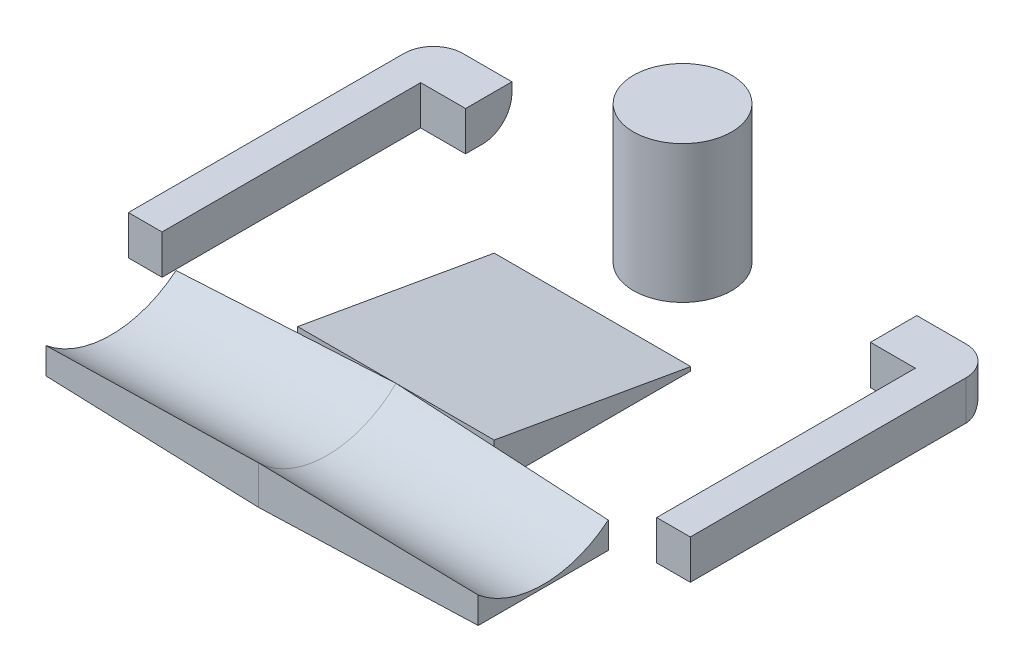
SolidWorks part; units mm, degrees
ref_plane "Front Plane" through (0, 0, 0) normal (0, 0, 1) x (1, 0, 0)
ref_plane "Top Plane" through (0, 0, 0) normal (0, 1, 0) x (1, 0, 0)
ref_plane "Right Plane" through (0, 0, 0) normal (1, 0, 0) x (0, 0, -1)
sketch "Sketch2" plane through (0, 0, 0) normal (0, 1, 0) x (1, 0, 0)
  line L0 (-95.95, 172.031) -> (-97.0155, 172.1902)
  line L1 (-97.0155, 172.1902) -> (-97.8001, 172.331)
  line L2 (95.95, 172.031) -> (97.0155, 172.1902)
  line L3 (97.0155, 172.1902) -> (97.8001, 172.331)
  line L4 (-106.3449, 171.5223) -> (-95.95, 171.5223)
  line L5 (-53.65, 171.5223) -> (-37.3449, 171.5223)
  line L6 (-37.3449, 189.5223) -> (-53.65, 189.5223)
  line L7 (-95.95, 189.5223) -> (-106.3449, 189.5223)
  line L8 (-106.3449, 179.9616) -> (-111.928, 179.9616)
  line L9 (-113.1433, 179.9616) -> (-121.3449, 179.9616)
  line L10 (-121.3449, 172.4616) -> (-106.3449, 172.4616)
  line L11 (-106.3449, 189.5223) -> (-106.3449, 176.1788)
  line L12 (-106.3449, 175.2767) -> (-106.3449, 171.5223)
  line L13 (-37.3449, 189.5223) -> (-37.3449, 181.131)
  line L14 (-37.3449, 180.0634) -> (-37.3449, 171.5223)
  line L15 (-121.3449, 172.4616) -> (-121.3449, 179.9616)
  line L16 (92.95, 159.181) -> (56.65, 159.181)
  line L17 (53.65, 162.181) -> (56.65, 159.181)
  line L18 (95.95, 198.481) -> (92.95, 201.481)
  line L19 (95.95, 172.331) -> (101.95, 172.331)
  line L20 (53.65, 198.481) -> (56.65, 201.481)
  line L21 (95.95, 198.481) -> (95.95, 188.331)
  line L22 (95.95, 172.331) -> (95.95, 162.181)
  line L23 (56.65, 201.481) -> (92.95, 201.481)
  line L24 (53.65, 162.181) -> (53.65, 198.481)
  line L25 (95.95, 162.181) -> (92.95, 159.181)
  line L26 (101.95, 188.331) -> (101.95, 172.331)
  line L27 (95.95, 188.331) -> (101.95, 188.331)
  line L28 (-53.65, 162.181) -> (-56.65, 159.181)
  line L29 (-56.65, 159.181) -> (-92.95, 159.181)
  line L30 (-95.95, 162.181) -> (-92.95, 159.181)
  line L31 (-95.95, 162.181) -> (-95.95, 172.331)
  line L32 (-95.95, 172.331) -> (-101.95, 172.331)
  line L33 (-101.95, 172.331) -> (-101.95, 188.331)
  line L34 (-95.95, 188.331) -> (-101.95, 188.331)
  line L35 (-95.95, 188.331) -> (-95.95, 198.481)
  line L36 (-53.65, 198.481) -> (-53.65, 162.181)
  line L37 (-92.95, 201.481) -> (-56.65, 201.481)
  line L38 (-95.95, 198.481) -> (-92.95, 201.481)
  line L39 (-53.65, 198.481) -> (-56.65, 201.481)
  line L40 (87.55, 164.831) -> (87.715, 164.831)
  line L41 (-56.55, 195.831) -> (-56.715, 195.831)
  line L42 (-87.55, 164.831) -> (-87.715, 164.831)
  line L43 (56.55, 164.831) -> (56.715, 164.831)
  line L44 (-87.55, 195.831) -> (-87.715, 195.831)
  line L45 (87.55, 195.831) -> (87.715, 195.831)
  line L46 (56.55, 195.831) -> (56.715, 195.831)
  line L47 (-56.55, 164.831) -> (-56.715, 164.831)
  line L48 (-15, 180.331) -> (-7, 180.331)
  line L49 (-32.5736, 137.9046) -> (-26.9167, 132.2478)
  line L50 (-75, 120.331) -> (-75, 112.331)
  line L51 (-117.4264, 137.9046) -> (-123.0833, 132.2478)
  line L52 (-135, 180.331) -> (-143, 180.331)
  line L53 (-117.4264, 222.7574) -> (-123.0833, 228.4143)
  line L54 (-75, 240.331) -> (-75, 248.331)
  line L55 (-32.5736, 222.7574) -> (-26.9167, 228.4143)
  line L56 (32.5736, 222.7574) -> (26.9167, 228.4143)
  line L57 (75, 240.331) -> (75, 248.331)
  line L58 (117.4264, 222.7574) -> (123.0833, 228.4143)
  line L59 (135, 180.331) -> (143, 180.331)
  line L60 (117.4264, 137.9046) -> (123.0833, 132.2478)
  line L61 (75, 120.331) -> (75, 112.331)
  line L62 (32.5736, 137.9046) -> (26.9167, 132.2478)
  line L63 (15, 180.331) -> (7, 180.331)
  circle A0 centre (90.3, 164.831) radius 2.585
  circle A1 centre (90.3, 164.831) radius 2.75
  circle A2 centre (-59.3, 195.831) radius 2.585
  circle A3 centre (-59.3, 195.831) radius 2.75
  circle A4 centre (-90.3, 164.831) radius 2.585
  circle A5 centre (-90.3, 164.831) radius 2.75
  circle A6 centre (59.3, 164.831) radius 2.585
  circle A7 centre (59.3, 164.831) radius 2.75
  circle A8 centre (-90.3, 195.831) radius 2.585
  circle A9 centre (-90.3, 195.831) radius 2.75
  circle A10 centre (90.3, 195.831) radius 2.585
  circle A11 centre (90.3, 195.831) radius 2.75
  circle A12 centre (59.3, 195.831) radius 2.585
  circle A13 centre (59.3, 195.831) radius 2.75
  circle A14 centre (-59.3, 164.831) radius 2.585
  circle A15 centre (-59.3, 164.831) radius 2.75
  arc A16 (59.3, 161.956) -> (59.3, 167.706) centre (59.3, 164.831) ccw
  arc A17 (59.3, 167.706) -> (59.3, 161.956) centre (59.3, 164.831) ccw
  arc A18 (90.3, 192.956) -> (90.3, 198.706) centre (90.3, 195.831) ccw
  arc A19 (90.3, 198.706) -> (90.3, 192.956) centre (90.3, 195.831) ccw
  arc A20 (59.3, 192.956) -> (59.3, 198.706) centre (59.3, 195.831) ccw
  arc A21 (59.3, 198.706) -> (59.3, 192.956) centre (59.3, 195.831) ccw
  arc A22 (90.3, 161.956) -> (90.3, 167.706) centre (90.3, 164.831) ccw
  arc A23 (90.3, 167.706) -> (90.3, 161.956) centre (90.3, 164.831) ccw
  arc A24 (-59.3, 198.706) -> (-59.3, 192.956) centre (-59.3, 195.831) ccw
  arc A25 (-59.3, 192.956) -> (-59.3, 198.706) centre (-59.3, 195.831) ccw
  arc A26 (-90.3, 198.706) -> (-90.3, 192.956) centre (-90.3, 195.831) ccw
  arc A27 (-90.3, 192.956) -> (-90.3, 198.706) centre (-90.3, 195.831) ccw
  arc A28 (-90.3, 167.706) -> (-90.3, 161.956) centre (-90.3, 164.831) ccw
  arc A29 (-90.3, 161.956) -> (-90.3, 167.706) centre (-90.3, 164.831) ccw
  arc A30 (-59.3, 167.706) -> (-59.3, 161.956) centre (-59.3, 164.831) ccw
  arc A31 (-59.3, 161.956) -> (-59.3, 167.706) centre (-59.3, 164.831) ccw
  arc A32 (91.55, 165.5527) -> (91.55, 164.1093) centre (90.3, 164.831) ccw
  arc A33 (91.55, 164.1093) -> (91.55, 165.5527) centre (90.3, 164.831) ccw
  arc A34 (-60.55, 196.5527) -> (-59.3, 197.2744) centre (-59.3, 195.831) ccw
  arc A35 (-59.3, 197.2744) -> (-60.55, 196.5527) centre (-59.3, 195.831) ccw
  arc A36 (-91.55, 165.5527) -> (-90.3, 166.2744) centre (-90.3, 164.831) ccw
  arc A37 (-90.3, 166.2744) -> (-91.55, 165.5527) centre (-90.3, 164.831) ccw
  arc A38 (60.55, 164.1093) -> (59.3, 163.3877) centre (59.3, 164.831) ccw
  arc A39 (59.3, 163.3877) -> (60.55, 164.1093) centre (59.3, 164.831) ccw
  arc A40 (-91.55, 196.5527) -> (-90.3, 197.2744) centre (-90.3, 195.831) ccw
  arc A41 (-90.3, 197.2744) -> (-91.55, 196.5527) centre (-90.3, 195.831) ccw
  arc A42 (91.55, 195.1093) -> (90.3, 194.3877) centre (90.3, 195.831) ccw
  arc A43 (90.3, 194.3877) -> (91.55, 195.1093) centre (90.3, 195.831) ccw
  arc A44 (60.55, 195.1093) -> (59.3, 194.3877) centre (59.3, 195.831) ccw
  arc A45 (59.3, 194.3877) -> (60.55, 195.1093) centre (59.3, 195.831) ccw
  arc A46 (-58.05, 165.5527) -> (-58.05, 164.1093) centre (-59.3, 164.831) ccw
  arc A47 (-58.05, 164.1093) -> (-58.05, 165.5527) centre (-59.3, 164.831) ccw
  arc A48 (-16.2563, 192.5448) -> (-7, 180.331) centre (1.2261, 196.1796) ccw
  arc A49 (-24.8255, 147.4294) -> (-26.9167, 132.2478) centre (-9.8933, 137.6376) ccw
  arc A50 (-62.7863, 121.5873) -> (-75, 112.331) centre (-59.1514, 104.1049) ccw
  arc A51 (-107.9017, 130.1565) -> (-123.0833, 132.2478) centre (-117.6934, 115.2243) ccw
  arc A52 (-133.7437, 168.1173) -> (-143, 180.331) centre (-151.2261, 164.4824) ccw
  arc A53 (-125.1745, 213.2327) -> (-123.0833, 228.4143) centre (-140.1067, 223.0244) ccw
  arc A54 (-87.2137, 239.0747) -> (-75, 248.331) centre (-90.8486, 256.5572) ccw
  arc A55 (-42.0983, 230.5055) -> (-26.9167, 228.4143) centre (-32.3066, 245.4377) ccw
  arc A56 (-42.0983, 230.5055) -> (-75, 240.331) centre (-75, 180.331) ccw
  arc A57 (-16.5125, 186.3853) -> (-35.0706, 223.4945) centre (-75, 180.331) ccw
  arc A58 (-37.9241, 225.9689) -> (-77.2868, 239.0865) centre (-75, 180.331) ccw
  arc A59 (-81.0542, 238.8185) -> (-118.1635, 220.2604) centre (-75, 180.331) ccw
  arc A60 (-120.6379, 217.4069) -> (-133.7555, 178.0442) centre (-75, 180.331) ccw
  arc A61 (-133.4875, 174.2768) -> (-114.9294, 137.1676) centre (-75, 180.331) ccw
  arc A62 (-112.0759, 134.6931) -> (-72.7132, 121.5755) centre (-75, 180.331) ccw
  arc A63 (-68.9458, 121.8435) -> (-31.8365, 140.4017) centre (-75, 180.331) ccw
  arc A64 (-29.3621, 143.2551) -> (-16.2445, 182.6179) centre (-75, 180.331) ccw
  arc A65 (-29.3621, 143.2551) -> (-53.65, 188.5756) centre (-58.2384, 156.9482) ccw
  arc A66 (-31.8365, 140.4017) -> (-53.65, 187.767) centre (-58.2384, 156.9482) ccw
  arc A67 (-68.9458, 121.8435) -> (-53.65, 170.4834) centre (-79.6819, 151.9447) ccw
  arc A68 (-72.7132, 121.5755) -> (-53.65, 169.0675) centre (-79.6819, 151.9447) ccw
  arc A69 (-112.0759, 134.6931) -> (-66.7271, 159.181) centre (-98.3828, 163.5694) ccw
  arc A70 (-114.9294, 137.1676) -> (-67.5349, 159.181) centre (-98.3828, 163.5694) ccw
  arc A71 (-133.4875, 174.2768) -> (-84.57, 159.181) centre (-103.3864, 185.0129) ccw
  arc A72 (-133.7555, 178.0442) -> (-85.9633, 159.181) centre (-103.3864, 185.0129) ccw
  arc A73 (-120.6379, 217.4069) -> (-101.95, 173.4229) centre (-91.7616, 203.7138) ccw
  arc A74 (-118.1635, 220.2604) -> (-101.95, 174.2682) centre (-91.7616, 203.7138) ccw
  arc A75 (-81.0542, 238.8185) -> (-95.95, 189.6295) centre (-70.3181, 208.7174) ccw
  arc A76 (-77.2868, 239.0865) -> (-95.95, 191.0014) centre (-70.3181, 208.7174) ccw
  arc A77 (-37.9241, 225.9689) -> (-83.2729, 201.481) centre (-51.6172, 197.0926) ccw
  arc A78 (-35.0706, 223.4945) -> (-82.4651, 201.481) centre (-51.6172, 197.0926) ccw
  arc A79 (-16.5125, 186.3853) -> (-65.43, 201.481) centre (-46.6136, 175.6491) ccw
  arc A80 (-16.2445, 182.6179) -> (-64.0367, 201.481) centre (-46.6136, 175.6491) ccw
  arc A81 (-16.2563, 192.5448) -> (-32.5736, 222.7574) centre (-75, 180.331) ccw
  arc A82 (-24.8255, 147.4294) -> (-15, 180.331) centre (-75, 180.331) ccw
  arc A83 (-107.9017, 130.1565) -> (-75, 120.331) centre (-75, 180.331) ccw
  arc A84 (-133.7437, 168.1173) -> (-117.4264, 137.9046) centre (-75, 180.331) ccw
  arc A85 (-125.1745, 213.2327) -> (-135, 180.331) centre (-75, 180.331) ccw
  arc A86 (-87.2137, 239.0747) -> (-117.4264, 222.7574) centre (-75, 180.331) ccw
  arc A87 (-62.7863, 121.5873) -> (-32.5736, 137.9046) centre (-75, 180.331) ccw
  arc A88 (26.9167, 228.4143) -> (42.0983, 230.5055) centre (32.3066, 245.4377) ccw
  arc A89 (75, 240.331) -> (42.0983, 230.5055) centre (75, 180.331) ccw
  arc A90 (75, 248.331) -> (87.2137, 239.0747) centre (90.8486, 256.5572) ccw
  arc A91 (117.4264, 222.7574) -> (87.2137, 239.0747) centre (75, 180.331) ccw
  arc A92 (123.0833, 228.4143) -> (125.1745, 213.2327) centre (140.1067, 223.0244) ccw
  arc A93 (135, 180.331) -> (125.1745, 213.2327) centre (75, 180.331) ccw
  arc A94 (143, 180.331) -> (133.7437, 168.1173) centre (151.2261, 164.4824) ccw
  arc A95 (117.4264, 137.9046) -> (133.7437, 168.1173) centre (75, 180.331) ccw
  arc A96 (123.0833, 132.2478) -> (107.9017, 130.1565) centre (117.6934, 115.2243) ccw
  arc A97 (75, 120.331) -> (107.9017, 130.1565) centre (75, 180.331) ccw
  arc A98 (75, 112.331) -> (62.7863, 121.5873) centre (59.1514, 104.1049) ccw
  arc A99 (32.5736, 137.9046) -> (62.7863, 121.5873) centre (75, 180.331) ccw
  arc A100 (26.9167, 132.2478) -> (24.8255, 147.4294) centre (9.8933, 137.6376) ccw
  arc A101 (15, 180.331) -> (24.8255, 147.4294) centre (75, 180.331) ccw
  arc A102 (7, 180.331) -> (16.2563, 192.5448) centre (-1.2261, 196.1796) ccw
  arc A103 (32.5736, 222.7574) -> (16.2563, 192.5448) centre (75, 180.331) ccw
  arc A104 (53.65, 170.4834) -> (68.9458, 121.8435) centre (79.6819, 151.9447) ccw
  arc A105 (53.65, 187.767) -> (31.8365, 140.4017) centre (58.2384, 156.9482) ccw
  arc A106 (53.65, 169.0675) -> (72.7132, 121.5755) centre (79.6819, 151.9447) ccw
  arc A107 (67.5349, 159.181) -> (114.9294, 137.1676) centre (98.3828, 163.5694) ccw
  arc A108 (85.9633, 159.181) -> (133.7555, 178.0442) centre (103.3864, 185.0129) ccw
  arc A109 (133.7555, 178.0442) -> (120.6379, 217.4069) centre (75, 180.331) ccw
  arc A110 (101.95, 174.2682) -> (118.1635, 220.2604) centre (91.7616, 203.7138) ccw
  arc A111 (95.95, 191.0014) -> (77.2868, 239.0865) centre (70.3181, 208.7174) ccw
  arc A112 (77.2868, 239.0865) -> (37.9241, 225.9689) centre (75, 180.331) ccw
  arc A113 (82.4651, 201.481) -> (35.0706, 223.4945) centre (51.6172, 197.0926) ccw
  arc A114 (64.0367, 201.481) -> (16.2445, 182.6179) centre (46.6136, 175.6491) ccw
  arc A115 (65.43, 201.481) -> (16.5125, 186.3853) centre (46.6136, 175.6491) ccw
  arc A116 (101.95, 173.4229) -> (120.6379, 217.4069) centre (91.7616, 203.7138) ccw
  arc A117 (35.0706, 223.4945) -> (16.5125, 186.3853) centre (75, 180.331) ccw
  arc A118 (95.95, 189.6295) -> (81.0542, 238.8185) centre (70.3181, 208.7174) ccw
  arc A119 (83.2729, 201.481) -> (37.9241, 225.9689) centre (51.6172, 197.0926) ccw
  arc A120 (118.1635, 220.2604) -> (81.0542, 238.8185) centre (75, 180.331) ccw
  arc A121 (114.9294, 137.1676) -> (133.4875, 174.2768) centre (75, 180.331) ccw
  arc A122 (72.7132, 121.5755) -> (112.0759, 134.6931) centre (75, 180.331) ccw
  arc A123 (31.8365, 140.4017) -> (68.9458, 121.8435) centre (75, 180.331) ccw
  arc A124 (16.2445, 182.6179) -> (29.3621, 143.2551) centre (75, 180.331) ccw
  arc A125 (53.65, 188.5756) -> (29.3621, 143.2551) centre (58.2384, 156.9482) ccw
  arc A126 (66.7271, 159.181) -> (112.0759, 134.6931) centre (98.3828, 163.5694) ccw
  arc A127 (84.57, 159.181) -> (133.4875, 174.2768) centre (103.3864, 185.0129) ccw
  spline S0 degree 3 poles (90.3, 163.3877) (90.4198, 163.4568) (90.6406, 163.5843) (90.9748, 163.7772) (91.2766, 163.9515) (91.454, 164.0539) (91.55, 164.1093) knots 0 0 0 0 0.300011 0.553083 0.757954 1 1 1 1
  spline S1 degree 3 poles (89.05, 164.1093) (89.1698, 164.0402) (89.3906, 163.9127) (89.7248, 163.7197) (90.0266, 163.5455) (90.204, 163.4431) (90.3, 163.3877) knots 0 0 0 0 0.300011 0.553083 0.757954 1 1 1 1
  spline S2 degree 3 poles (89.05, 165.5527) (89.05, 165.4144) (89.05, 165.1594) (89.05, 164.7735) (89.05, 164.425) (89.05, 164.2202) (89.05, 164.1093) knots 0 0 0 0 0.300011 0.553083 0.757954 1 1 1 1
  spline S3 degree 3 poles (90.3, 166.2744) (90.1802, 166.2052) (89.9594, 166.0777) (89.6252, 165.8848) (89.3234, 165.7106) (89.146, 165.6082) (89.05, 165.5527) knots 0 0 0 0 0.300011 0.553083 0.757954 1 1 1 1
  spline S4 degree 3 poles (91.55, 165.5527) (91.4302, 165.6219) (91.2094, 165.7494) (90.8752, 165.9423) (90.5734, 166.1166) (90.396, 166.2189) (90.3, 166.2744) knots 0 0 0 0 0.300011 0.553083 0.757954 1 1 1 1
  spline S5 degree 3 poles (91.55, 164.1093) (91.55, 164.2477) (91.55, 164.5027) (91.55, 164.8885) (91.55, 165.237) (91.55, 165.4418) (91.55, 165.5527) knots 0 0 0 0 0.300011 0.553083 0.757954 1 1 1 1
  spline S6 degree 3 poles (-58.05, 196.5527) (-58.1698, 196.6219) (-58.3906, 196.7494) (-58.7248, 196.9423) (-59.0266, 197.1166) (-59.204, 197.2189) (-59.3, 197.2744) knots 0 0 0 0 0.300011 0.553083 0.757954 1 1 1 1
  spline S7 degree 3 poles (-58.05, 195.1093) (-58.05, 195.2477) (-58.05, 195.5027) (-58.05, 195.8885) (-58.05, 196.237) (-58.05, 196.4418) (-58.05, 196.5527) knots 0 0 0 0 0.300011 0.553083 0.757954 1 1 1 1
  spline S8 degree 3 poles (-59.3, 194.3877) (-59.1802, 194.4568) (-58.9594, 194.5843) (-58.6252, 194.7772) (-58.3234, 194.9515) (-58.146, 195.0539) (-58.05, 195.1093) knots 0 0 0 0 0.300011 0.553083 0.757954 1 1 1 1
  spline S9 degree 3 poles (-60.55, 195.1093) (-60.4302, 195.0402) (-60.2094, 194.9127) (-59.8752, 194.7197) (-59.5734, 194.5455) (-59.396, 194.4431) (-59.3, 194.3877) knots 0 0 0 0 0.300011 0.553083 0.757954 1 1 1 1
  spline S10 degree 3 poles (-60.55, 196.5527) (-60.55, 196.4144) (-60.55, 196.1594) (-60.55, 195.7735) (-60.55, 195.425) (-60.55, 195.2202) (-60.55, 195.1093) knots 0 0 0 0 0.300011 0.553083 0.757954 1 1 1 1
  spline S11 degree 3 poles (-59.3, 197.2744) (-59.4198, 197.2052) (-59.6406, 197.0777) (-59.9748, 196.8848) (-60.2766, 196.7106) (-60.454, 196.6082) (-60.55, 196.5527) knots 0 0 0 0 0.300011 0.553083 0.757954 1 1 1 1
  spline S12 degree 3 poles (-89.05, 165.5527) (-89.1698, 165.6219) (-89.3906, 165.7494) (-89.7248, 165.9423) (-90.0266, 166.1166) (-90.204, 166.2189) (-90.3, 166.2744) knots 0 0 0 0 0.300011 0.553083 0.757954 1 1 1 1
  spline S13 degree 3 poles (-89.05, 164.1093) (-89.05, 164.2477) (-89.05, 164.5027) (-89.05, 164.8885) (-89.05, 165.237) (-89.05, 165.4418) (-89.05, 165.5527) knots 0 0 0 0 0.300011 0.553083 0.757954 1 1 1 1
  spline S14 degree 3 poles (-90.3, 163.3877) (-90.1802, 163.4568) (-89.9594, 163.5843) (-89.6252, 163.7772) (-89.3234, 163.9515) (-89.146, 164.0539) (-89.05, 164.1093) knots 0 0 0 0 0.300011 0.553083 0.757954 1 1 1 1
  spline S15 degree 3 poles (-91.55, 165.5527) (-91.55, 165.4144) (-91.55, 165.1594) (-91.55, 164.7735) (-91.55, 164.425) (-91.55, 164.2202) (-91.55, 164.1093) knots 0 0 0 0 0.300011 0.553083 0.757954 1 1 1 1
  spline S16 degree 3 poles (-91.55, 164.1093) (-91.4302, 164.0402) (-91.2094, 163.9127) (-90.8752, 163.7197) (-90.5734, 163.5455) (-90.396, 163.4431) (-90.3, 163.3877) knots 0 0 0 0 0.300011 0.553083 0.757954 1 1 1 1
  spline S17 degree 3 poles (-90.3, 166.2744) (-90.4198, 166.2052) (-90.6406, 166.0777) (-90.9748, 165.8848) (-91.2766, 165.7106) (-91.454, 165.6082) (-91.55, 165.5527) knots 0 0 0 0 0.300011 0.553083 0.757954 1 1 1 1
  spline S18 degree 3 poles (58.05, 164.1093) (58.1698, 164.0402) (58.3906, 163.9127) (58.7248, 163.7197) (59.0266, 163.5455) (59.204, 163.4431) (59.3, 163.3877) knots 0 0 0 0 0.300011 0.553083 0.757954 1 1 1 1
  spline S19 degree 3 poles (58.05, 165.5527) (58.05, 165.4144) (58.05, 165.1594) (58.05, 164.7735) (58.05, 164.425) (58.05, 164.2202) (58.05, 164.1093) knots 0 0 0 0 0.300011 0.553083 0.757954 1 1 1 1
  spline S20 degree 3 poles (59.3, 166.2744) (59.1802, 166.2052) (58.9594, 166.0777) (58.6252, 165.8848) (58.3234, 165.7106) (58.146, 165.6082) (58.05, 165.5527) knots 0 0 0 0 0.300011 0.553083 0.757954 1 1 1 1
  spline S21 degree 3 poles (60.55, 165.5527) (60.4302, 165.6219) (60.2094, 165.7494) (59.8752, 165.9423) (59.5734, 166.1166) (59.396, 166.2189) (59.3, 166.2744) knots 0 0 0 0 0.300011 0.553083 0.757954 1 1 1 1
  spline S22 degree 3 poles (60.55, 164.1093) (60.55, 164.2477) (60.55, 164.5027) (60.55, 164.8885) (60.55, 165.237) (60.55, 165.4418) (60.55, 165.5527) knots 0 0 0 0 0.300011 0.553083 0.757954 1 1 1 1
  spline S23 degree 3 poles (59.3, 163.3877) (59.4198, 163.4568) (59.6406, 163.5843) (59.9748, 163.7772) (60.2766, 163.9515) (60.454, 164.0539) (60.55, 164.1093) knots 0 0 0 0 0.300011 0.553083 0.757954 1 1 1 1
  spline S24 degree 3 poles (-89.05, 196.5527) (-89.1698, 196.6219) (-89.3906, 196.7494) (-89.7248, 196.9423) (-90.0266, 197.1166) (-90.204, 197.2189) (-90.3, 197.2744) knots 0 0 0 0 0.300011 0.553083 0.757954 1 1 1 1
  spline S25 degree 3 poles (-91.55, 195.1093) (-91.4302, 195.0402) (-91.2094, 194.9127) (-90.8752, 194.7197) (-90.5734, 194.5455) (-90.396, 194.4431) (-90.3, 194.3877) knots 0 0 0 0 0.300011 0.553083 0.757954 1 1 1 1
  spline S26 degree 3 poles (-89.05, 195.1093) (-89.05, 195.2477) (-89.05, 195.5027) (-89.05, 195.8885) (-89.05, 196.237) (-89.05, 196.4418) (-89.05, 196.5527) knots 0 0 0 0 0.300011 0.553083 0.757954 1 1 1 1
  spline S27 degree 3 poles (-90.3, 194.3877) (-90.1802, 194.4568) (-89.9594, 194.5843) (-89.6252, 194.7772) (-89.3234, 194.9515) (-89.146, 195.0539) (-89.05, 195.1093) knots 0 0 0 0 0.300011 0.553083 0.757954 1 1 1 1
  spline S28 degree 3 poles (-91.55, 196.5527) (-91.55, 196.4144) (-91.55, 196.1594) (-91.55, 195.7735) (-91.55, 195.425) (-91.55, 195.2202) (-91.55, 195.1093) knots 0 0 0 0 0.300011 0.553083 0.757954 1 1 1 1
  spline S29 degree 3 poles (-90.3, 197.2744) (-90.4198, 197.2052) (-90.6406, 197.0777) (-90.9748, 196.8848) (-91.2766, 196.7106) (-91.454, 196.6082) (-91.55, 196.5527) knots 0 0 0 0 0.300011 0.553083 0.757954 1 1 1 1
  spline S30 degree 3 poles (89.05, 195.1093) (89.1698, 195.0402) (89.3906, 194.9127) (89.7248, 194.7197) (90.0266, 194.5455) (90.204, 194.4431) (90.3, 194.3877) knots 0 0 0 0 0.300011 0.553083 0.757954 1 1 1 1
  spline S31 degree 3 poles (91.55, 196.5527) (91.4302, 196.6219) (91.2094, 196.7494) (90.8752, 196.9423) (90.5734, 197.1166) (90.396, 197.2189) (90.3, 197.2744) knots 0 0 0 0 0.300011 0.553083 0.757954 1 1 1 1
  spline S32 degree 3 poles (91.55, 195.1093) (91.55, 195.2477) (91.55, 195.5027) (91.55, 195.8885) (91.55, 196.237) (91.55, 196.4418) (91.55, 196.5527) knots 0 0 0 0 0.300011 0.553083 0.757954 1 1 1 1
  spline S33 degree 3 poles (90.3, 197.2744) (90.1802, 197.2052) (89.9594, 197.0777) (89.6252, 196.8848) (89.3234, 196.7106) (89.146, 196.6082) (89.05, 196.5527) knots 0 0 0 0 0.300011 0.553083 0.757954 1 1 1 1
  spline S34 degree 3 poles (89.05, 196.5527) (89.05, 196.4144) (89.05, 196.1594) (89.05, 195.7735) (89.05, 195.425) (89.05, 195.2202) (89.05, 195.1093) knots 0 0 0 0 0.300011 0.553083 0.757954 1 1 1 1
  spline S35 degree 3 poles (90.3, 194.3877) (90.4198, 194.4568) (90.6406, 194.5843) (90.9748, 194.7772) (91.2766, 194.9515) (91.454, 195.0539) (91.55, 195.1093) knots 0 0 0 0 0.300011 0.553083 0.757954 1 1 1 1
  spline S36 degree 3 poles (58.05, 195.1093) (58.1698, 195.0402) (58.3906, 194.9127) (58.7248, 194.7197) (59.0266, 194.5455) (59.204, 194.4431) (59.3, 194.3877) knots 0 0 0 0 0.300011 0.553083 0.757954 1 1 1 1
  spline S37 degree 3 poles (58.05, 196.5527) (58.05, 196.4144) (58.05, 196.1594) (58.05, 195.7735) (58.05, 195.425) (58.05, 195.2202) (58.05, 195.1093) knots 0 0 0 0 0.300011 0.553083 0.757954 1 1 1 1
  spline S38 degree 3 poles (59.3, 197.2744) (59.1802, 197.2052) (58.9594, 197.0777) (58.6252, 196.8848) (58.3234, 196.7106) (58.146, 196.6082) (58.05, 196.5527) knots 0 0 0 0 0.300011 0.553083 0.757954 1 1 1 1
  spline S39 degree 3 poles (60.55, 196.5527) (60.4302, 196.6219) (60.2094, 196.7494) (59.8752, 196.9423) (59.5734, 197.1166) (59.396, 197.2189) (59.3, 197.2744) knots 0 0 0 0 0.300011 0.553083 0.757954 1 1 1 1
  spline S40 degree 3 poles (60.55, 195.1093) (60.55, 195.2477) (60.55, 195.5027) (60.55, 195.8885) (60.55, 196.237) (60.55, 196.4418) (60.55, 196.5527) knots 0 0 0 0 0.300011 0.553083 0.757954 1 1 1 1
  spline S41 degree 3 poles (59.3, 194.3877) (59.4198, 194.4568) (59.6406, 194.5843) (59.9748, 194.7772) (60.2766, 194.9515) (60.454, 195.0539) (60.55, 195.1093) knots 0 0 0 0 0.300011 0.553083 0.757954 1 1 1 1
  spline S42 degree 3 poles (-59.3, 163.3877) (-59.1802, 163.4568) (-58.9594, 163.5843) (-58.6252, 163.7772) (-58.3234, 163.9515) (-58.146, 164.0539) (-58.05, 164.1093) knots 0 0 0 0 0.300011 0.553083 0.757954 1 1 1 1
  spline S43 degree 3 poles (-60.55, 164.1093) (-60.4302, 164.0402) (-60.2094, 163.9127) (-59.8752, 163.7197) (-59.5734, 163.5455) (-59.396, 163.4431) (-59.3, 163.3877) knots 0 0 0 0 0.300011 0.553083 0.757954 1 1 1 1
  spline S44 degree 3 poles (-60.55, 165.5527) (-60.55, 165.4144) (-60.55, 165.1594) (-60.55, 164.7735) (-60.55, 164.425) (-60.55, 164.2202) (-60.55, 164.1093) knots 0 0 0 0 0.300011 0.553083 0.757954 1 1 1 1
  spline S45 degree 3 poles (-59.3, 166.2744) (-59.4198, 166.2052) (-59.6406, 166.0777) (-59.9748, 165.8848) (-60.2766, 165.7106) (-60.454, 165.6082) (-60.55, 165.5527) knots 0 0 0 0 0.300011 0.553083 0.757954 1 1 1 1
  spline S46 degree 3 poles (-58.05, 165.5527) (-58.1698, 165.6219) (-58.3906, 165.7494) (-58.7248, 165.9423) (-59.0266, 166.1166) (-59.204, 166.2189) (-59.3, 166.2744) knots 0 0 0 0 0.300011 0.553083 0.757954 1 1 1 1
  spline S47 degree 3 poles (-58.05, 164.1093) (-58.05, 164.2477) (-58.05, 164.5027) (-58.05, 164.8885) (-58.05, 165.237) (-58.05, 165.4418) (-58.05, 165.5527) knots 0 0 0 0 0.300011 0.553083 0.757954 1 1 1 1
sketch "Sketch3" plane through (0, 0, 0) normal (0, 1, 0) x (1, 0, 0)
  line L0 (0, -74.8) -> (0, 74.8) construction
  line L1 (-35, 263.5635) -> (35, 263.5635)
  line L2 (-35, 263.5635) -> (-35, 213.5635)
  line L3 (-35, 213.5635) -> (35, 213.5635)
  line L4 (35, 263.5635) -> (35, 213.5635)
  line L5 (-35, 263.5635) -> (35, 213.5635) construction
  line L6 (-35, 213.5635) -> (35, 263.5635) construction
  line L7 (-143, 248.331) -> (-143, 93.0882)
  line L8 (-143, 248.331) -> (-103.0473, 248.331)
  line L9 (-103.0473, 248.331) -> (-103.0473, 224.7437)
  line L10 (-103.0473, 224.7437) -> (-125.8851, 224.7437)
  line L11 (-125.8851, 224.7437) -> (-125.8851, 93.0882)
  line L12 (143, 248.331) -> (143, 93.0882)
  line L13 (143, 248.331) -> (103.0473, 248.331)
  line L14 (103.0473, 248.331) -> (103.0473, 224.7437)
  line L15 (103.0473, 224.7437) -> (125.8851, 224.7437)
  line L16 (125.8851, 224.7437) -> (125.8851, 93.0882)
  line L17 (-143, 93.0882) -> (-125.8851, 93.0882)
  line L18 (125.8851, 93.0882) -> (143, 93.0882)
  point P0 (0, 238.5635)
extrude "Boss-Extrude1" add sketch "Sketch3" along normal blind 20 contours L7 L17 L11 L10 L9 L8 | L16 L18 L12 L13 L14 L15
fillet "Fillet1" radius 15 2 edges at (-123.0236, 0, -248.331) (-143, 10, -248.331)
fillet "Fillet2" radius 15 2 edges at (143, 10, -248.331) (123.0236, 0, -248.331)
ref_plane "Plane2" through (0, 61.864, -10.9083) normal (0, 0.9848, -0.1736) x (-1, 0, 0)
sketch "Sketch4" plane through (0, 0, 0) normal (0, 1, 0) x (1, 0, 0)
  line L0 (0, -11) -> (0, 11) construction
  line L1 (-43.8326, 86.2523) -> (43.8326, 86.2523)
  line L2 (-43.8326, 86.2523) -> (-43.8326, 180.1113)
  line L3 (-43.8326, 180.1113) -> (43.8326, 180.1113)
  line L4 (43.8326, 86.2523) -> (43.8326, 180.1113)
  line L5 (-43.8326, 86.2523) -> (43.8326, 180.1113) construction
  line L6 (-43.8326, 180.1113) -> (43.8326, 86.2523) construction
  circle A0 centre (0, 232.1516) radius 25
  point P0 (0, 133.1818)
sketch "Sketch5" plane through (0, 0, 0) normal (1, 0, 0) x (0, 0, -1)
  line L1 (86.2523, 19.644) -> (86.2523, 0)
  line L2 (86.2523, 0) -> (186.3163, 0)
  line L3 (186.3163, 0) -> (186.3163, 2)
  line L4 (186.3163, 2) -> (86.2523, 19.644)
  dimension "D1" = 2
  dimension "D2" = 10
extrude "Boss-Extrude2" add sketch "Sketch5" along normal mid plane 100 separate body
extrude "Boss-Extrude3" add sketch "Sketch4" along normal blind 70 separate body contours A0
sketch "Sketch6" plane through (0, 0, 0) normal (1, 0, 0) x (0, 0, -1)
  line L0 (86.2523, 0) -> (16.2326, 0)
  line L1 (16.2326, 0) -> (16.2326, 19.644)
  line L2 (86.2523, 19.644) -> (86.2523, 0)
  arc A0 (16.2326, 19.644) -> (86.2523, 19.644) centre (51.2424, 55.3415) ccw
extrude "Boss-Extrude4" add sketch "Sketch6" along normal mid plane 220 draft 1
